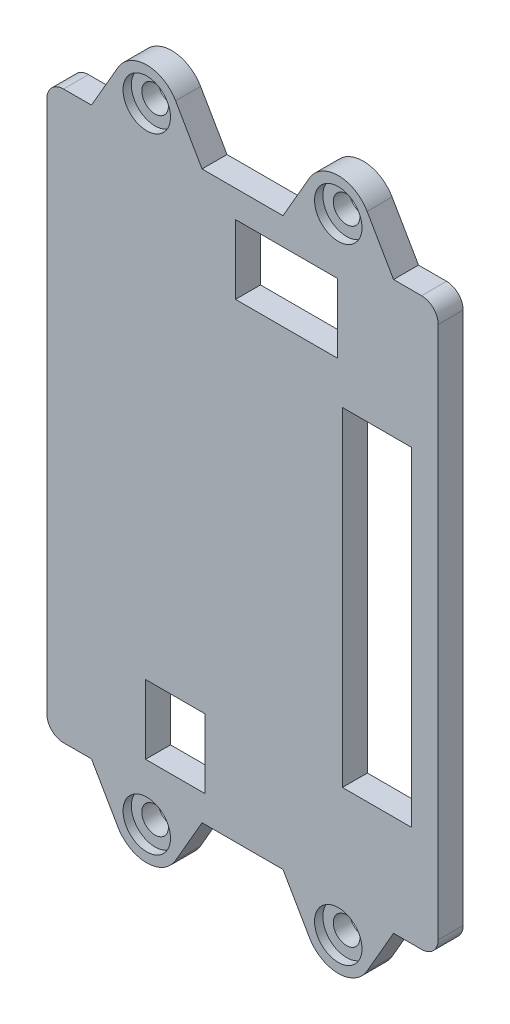
SolidWorks part; units mm, degrees
ref_plane "前视基准面" through (0, 0, 0) normal (0, 0, 1) x (1, 0, 0)
ref_plane "上视基准面" through (0, 0, 0) normal (0, 1, 0) x (1, 0, 0)
ref_plane "右视基准面" through (0, 0, 0) normal (1, 0, 0) x (0, 0, -1)
sketch "草图1" plane through (0, 0, 0) normal (0, 0, 1) x (1, 0, 0)
  line L0 (-23.5, -34) -> (-23.5, 34)
  line L1 (-20.5, -31) -> (20.5, -31) construction
  line L2 (-20.5, -31) -> (-20.5, 31) construction
  line L3 (-20.5, 31) -> (20.5, 31) construction
  line L4 (20.5, -31) -> (20.5, 31) construction
  line L5 (-20.5, -31) -> (20.5, 31) construction
  line L6 (-20.5, 31) -> (20.5, -31) construction
  line L7 (-23.5, 34) -> (23.5, 34)
  line L8 (23.5, -34) -> (23.5, 34)
  line L9 (-23.5, -34) -> (23.5, -34)
  line L12 (0, 0) -> (0, 18.7905) construction
  line L14 (0, 0) -> (13.8633, 0) construction
  point P0 (0, 0)
  dimension "D2" = 41
  dimension "D4" = 62
  dimension "D1" = 3
extrude "凸台-拉伸1" add sketch "草图1" along normal blind 3
sketch "草图3" plane through (0, 0, 3) normal (0, 0, 1) x (1, 0, 0)
  line L0 (-18.1395, 34) -> (-14.9641, 39.5)
  line L1 (-8.0359, 39.5) -> (-4.8605, 34)
  line L2 (-23.5, 34) -> (-23.5, -34) construction
  line L3 (23.5, 34) -> (-23.5, 34) construction
  line L4 (-18.1395, 34) -> (-4.8605, 34)
  circle A0 centre (-11.5, 37.5) radius 1.6
  arc A1 (-14.9641, 39.5) -> (-8.0359, 39.5) centre (-11.5, 37.5) cw
  dimension "D1" = 3.2
  dimension "D2" = 4
  dimension "D3" = 60
  dimension "D4" = 12
  dimension "D5" = 3.5
extrude "凸台-拉伸2" add sketch "草图3" against normal through all
mirror "镜向1" about plane through (0, 0, 0) normal (0, 1, 0) of "凸台-拉伸2"
mirror "镜向2" about plane through (0, 0, 0) normal (1, 0, 0) of "镜向1"
sketch "草图2" plane through (0, 0, 3) normal (0, 0, 1) x (1, 0, 0)
  circle A0 centre (-11.5, 37.5) radius 2.85
  circle A1 centre (11.5, 37.5) radius 2.85
  circle A2 centre (11.5, -37.5) radius 2.85
  circle A3 centre (-11.5, -37.5) radius 2.85
  point P12 (-11.5, 37.5)
  point P14 (11.5, 37.5)
  point P16 (11.5, -37.5)
  point P18 (-11.5, -37.5)
  dimension "D1" = 5.7
extrude "切除-拉伸1" cut sketch "草图2" against normal blind 1
fillet "圆角1" radius 2 4 edges at (23.5, -34, 1.5) (23.5, 34, 1.5) (-23.5, -34, 1.5) (-23.5, 34, 1.5)
sketch "草图4" plane through (0, 0, 3) normal (0, 0, 1) x (1, 0, 0)
  line L0 (-11.644, -30.7939) -> (-11.644, -22.4939)
  line L1 (-11.544, -30.6939) -> (-4.604, -30.6939) construction
  line L2 (-11.544, -30.6939) -> (-11.544, -22.5939) construction
  line L3 (-11.544, -22.5939) -> (-4.604, -22.5939) construction
  line L4 (-4.604, -30.6939) -> (-4.604, -22.5939) construction
  line L5 (20.1959, -21.8033) -> (12.0959, -21.8033) construction
  line L6 (20.1959, -21.8033) -> (20.1959, 17.523) construction
  line L7 (20.1959, 17.523) -> (12.0959, 17.523) construction
  line L8 (12.0959, -21.8033) -> (12.0959, 17.523) construction
  line L9 (-0.74, 22.5469) -> (11.28, 22.5469) construction
  line L10 (-0.74, 22.5469) -> (-0.74, 30.6469) construction
  line L11 (-0.74, 30.6469) -> (11.28, 30.6469) construction
  line L12 (11.28, 22.5469) -> (11.28, 30.6469) construction
  line L13 (-11.644, -22.4939) -> (-4.504, -22.4939)
  line L14 (-4.504, -30.7939) -> (-4.504, -22.4939)
  line L15 (-11.644, -30.7939) -> (-4.504, -30.7939)
  line L16 (-0.84, 22.4469) -> (-0.84, 30.7469)
  line L17 (-0.84, 30.7469) -> (11.38, 30.7469)
  line L18 (11.38, 22.4469) -> (11.38, 30.7469)
  line L19 (-0.84, 22.4469) -> (11.38, 22.4469)
  line L20 (20.2959, -21.9033) -> (20.2959, 17.623)
  line L21 (20.2959, 17.623) -> (11.9959, 17.623)
  line L22 (11.9959, -21.9033) -> (11.9959, 17.623)
  line L23 (20.2959, -21.9033) -> (11.9959, -21.9033)
  line L24 (-20.5, -31) -> (20.5, -31) construction
  line L25 (-20.5, -31) -> (-20.5, 31) construction
  line L26 (-20.5, 31) -> (20.5, 31) construction
  line L27 (20.5, -31) -> (20.5, 31) construction
  line L28 (-20.5, 31) -> (20.5, -31) construction
  line L29 (0, 0) -> (-20.5, -31) construction
extrude "切除-拉伸2" cut sketch "草图4" against normal through all
